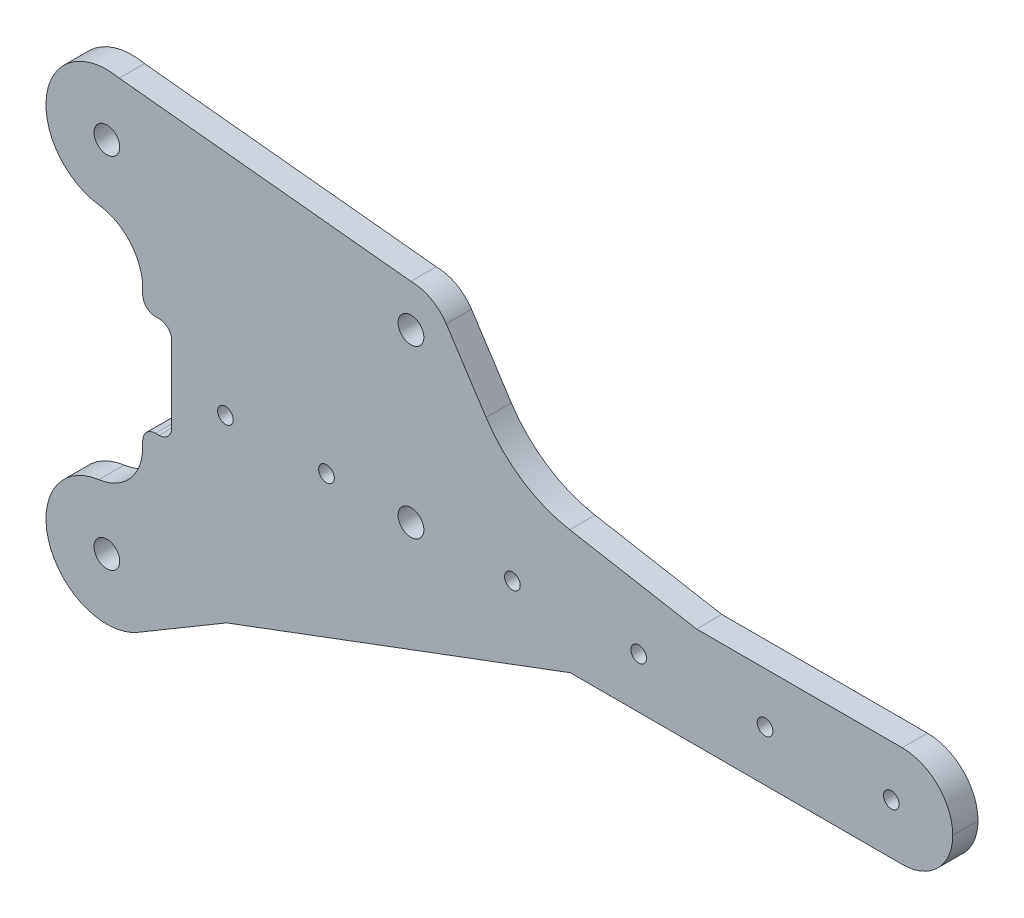
SolidWorks part; units mm, degrees
ref_plane "Alzado" through (0, 0, 0) normal (0, 0, 1) x (1, 0, 0)
ref_plane "Planta" through (0, 0, 0) normal (0, 1, 0) x (1, 0, 0)
ref_plane "Vista lateral" through (0, 0, 0) normal (1, 0, 0) x (0, 0, -1)
sketch "Croquis1" plane through (0, 0, 0) normal (0, 0, 1) x (1, 0, 0)
  line L0 (22.5, 23.4488) -> (22.5, 10)
  line L1 (22.5, 10) -> (28.2331, 10)
  line L2 (28.2331, 10) -> (28.2331, -10)
  line L3 (28.2331, -10) -> (22.5, -10)
  line L4 (15.4, -22.5) -> (15.4, -35.5)
  line L8 (30, 0) -> (168.0519, 0) construction
  line L9 (23.6157, 44.6413) -> (82.1332, 10)
  line L10 (87.5, 10) -> (182.8501, 10)
  line L12 (82.1332, -10) -> (182.8501, -10)
  line L13 (22.5, -10) -> (22.5, -20.5)
  line L14 (15.4, 23.4488) -> (22.5, 23.4488)
  line L16 (23.6157, -44.6413) -> (79.7406, -11.4164)
  line L17 (21.6105, -45.8277) -> (23.6157, -44.6413)
  line L18 (15.4, -23.4488) -> (22.5, -23.4488)
  line L19 (22.5, -23.4488) -> (22.5, -20.5)
  line L20 (79.7406, -11.4164) -> (82.1332, -10)
  line L28 (0, -37.5) -> (0, -37.5736)
  line L33 (23.6157, 44.6413) -> (21.6105, 45.8277)
  line L39 (182.8501, 10) -> (182.8501, -10)
  line L40 (82.1332, 10) -> (87.5, 10)
  circle A0 centre (170.6863, 0) radius 1.55
  circle A3 centre (75.6, 0) radius 2.55
  circle A4 centre (15.4, -35.5) radius 2.55
  circle A5 centre (15.4, 35.5) radius 2.55
  arc A8 (21.6105, 45.8277) -> (15.4, 23.4488) centre (15.4, 35.5) ccw
  arc A9 (21.6105, -45.8277) -> (15.4, -23.4488) centre (15.4, -35.5) cw
  circle A10 centre (95.6863, 0) radius 1.55
  circle A12 centre (145.6863, 0) radius 1.55
  circle A13 centre (120.6863, 0) radius 1.55
  circle A14 centre (38.875, 0) radius 1.55
  circle A15 centre (58.875, 0) radius 1.55
  dimension "D4" = 10
  dimension "D1" = 5.1
  dimension "D3" = 3.1
  dimension "D5" = 3.1
  dimension "D6" = 3.1
  dimension "D7" = 3.1
  dimension "D8" = 3.1
  dimension "D13" = 3.1
  dimension "D2" = 20
  dimension "D9" = 20
  dimension "D10" = 25
  dimension "D11" = 25
  dimension "D12" = 25
  dimension "D14" = 60.2
extrude "Saliente-Extruir1" add sketch "Croquis1" along normal blind 5 contours A3 L39 L10 L40 L9 L33 A8 L14 L0 L1 L2 L3 L13 L19 L18 A4 A9 L17 L16 L20 L12 A5 region at (71.3748, 0, 0)
fillet "Redondeo1" radius 10 2 edges at (22.5, -23.4488, 2.5) (22.5, 23.4488, 2.5)
fillet "Redondeo2" radius 10 2 edges at (182.8501, -10, 2.5) (182.8501, 10, 2.5)
fillet "Redondeo4" radius 2.5 4 edges at (28.2331, -10, 2.5) (28.2331, 10, 2.5) (22.5, 10, 2.5) (22.5, -10, 2.5)
chamfer "Chaflán1" distance 50 distance2 25 2 edges at (82.1332, -10, 2.5) (82.1332, 10, 2.5) first distance on face at (52.8745, -27.3207, 2.5) first distance on face at (127.4917, 10, 2.5)
sketch "Croquis2" plane through (0, 0, 0) normal (0, 0, -1) x (-1, 0, 0)
  line L0 (-75.6, 0) -> (-75.6, 52.1416) construction
  line L1 (-96.3767, 16.3677) -> (-82.5829, 37.5477)
  line L3 (-75.6, 41.3332) -> (-15.4, 47.5512)
  line L4 (-60.6202, 22.7353) -> (-132.1332, 10) construction
  line L5 (-96.3767, 16.3677) -> (-60.6202, 22.7353)
  line L6 (-60.6202, 22.7353) -> (-15.4, 47.5512)
  line L7 (-15.4, 35.5) -> (-15.4, -35.5) construction
  line L8 (-74.6861, 0) -> (-38.875, 0) construction
  line L9 (-75.6, 33) -> (-15.4, 33) construction
  circle A0 centre (-75.6, 33) radius 2.55
  circle A1 centre (-75.6, 0) radius 2.55 construction
  arc A3 (-75.6, 41.3332) -> (-82.5829, 37.5477) centre (-75.6, 33) ccw
  arc A4 (-13.8151, 23.5534) -> (-21.6105, 45.8277) centre (-15.4, 35.5) ccw construction
  dimension "D1" = 5.1
  dimension "D2" = 33
  dimension "D3" = 60.2
extrude "Saliente-Extruir2" add sketch "Croquis2" against normal up to surface (5 mm away) up to face at (60.425, 0, 5)
fillet "Redondeo5" radius 25 1 edges at (96.3767, 16.3677, 2.5)
